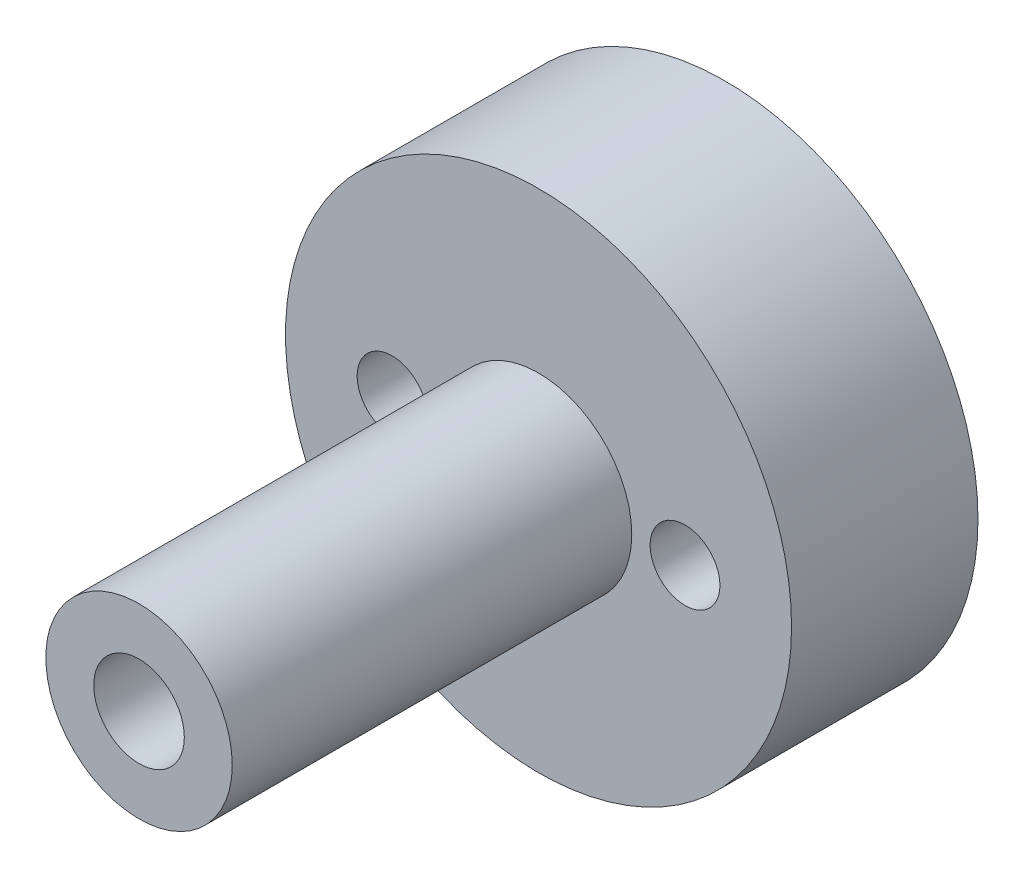
SolidWorks part; units mm, degrees
ref_plane "Front Plane" through (0, 0, 0) normal (0, 0, 1) x (1, 0, 0)
ref_plane "Top Plane" through (0, 0, 0) normal (0, 1, 0) x (1, 0, 0)
ref_plane "Right Plane" through (0, 0, 0) normal (1, 0, 0) x (0, 0, -1)
sketch "Sketch1" plane through (0, 0, 0) normal (0, 0, 1) x (1, 0, 0)
  circle A0 centre (0, 0) radius 7.6
  circle A1 centre (0, 0) radius 9.5
  dimension "D1" = 15.2
  dimension "D2" = 19
extrude "Boss-Extrude1" add sketch "Sketch1" along normal blind 5
sketch "Sketch2" plane through (0, 0, 5) normal (0, 0, 1) x (1, 0, 0)
  circle A0 centre (0, 0) radius 9.5 construction
  circle A1 centre (0, 0) radius 9.5
  circle A2 centre (0, 0) radius 1.31
  dimension "D1" = 2.62
extrude "Boss-Extrude2" add sketch "Sketch2" along normal blind 2
sketch "Sketch3" plane through (0, 0, 7) normal (0, 0, 1) x (1, 0, 0)
  circle A0 centre (-5.5, 0) radius 1.31
  circle A1 centre (5.5, 0) radius 1.31
  circle A2 centre (0, 0) radius 1.31 construction
  circle A3 centre (0, 0) radius 1.7
  circle A4 centre (0, 0) radius 3.5
  dimension "D1" = 5.5
  dimension "D3" = 3.4
  dimension "D4" = 7
  dimension "D2" = 5.5
extrude "Boss-Extrude3" add sketch "Sketch3" along normal blind 15 contours A4 A3 region at (-3.401, 0, 7)
extrude "Cut-Extrude1" cut sketch "Sketch3<3>" against normal through all both and the other way through all contours A0 | A1 region at (-5.5, 0, 7)
sketch "Sketch3<3>" plane through (0, 0, 7) normal (0, 0, 1) x (1, 0, 0) same geometry as "Sketch3"
sketch "Sketch4" plane through (0, 0, 5) normal (0, 0, -1) x (-1, 0, 0)
  circle A0 centre (-5.5, 0) radius 1.31 construction
  circle A1 centre (5.5, 0) radius 1.31 construction
  circle A2 centre (0, 0) radius 1.31 construction
  circle A3 centre (-5.5, 0) radius 1.31
  circle A4 centre (5.5, 0) radius 1.31
  circle A5 centre (0, 0) radius 1.31
  circle A6 centre (5.5, 0) radius 1.81
  circle A7 centre (0, 0) radius 1.81
  circle A8 centre (-5.5, 0) radius 1.81
  dimension "D1" = 0.5
extrude "Boss-Extrude4" add sketch "Sketch4" along normal up to surface (5 mm away) up to face at (9.5, 0, 0)
sketch "Sketch5" plane through (0, 0, 5) normal (0, 0, -1) x (-1, 0, 0)
  circle A0 centre (5.5, 0) radius 1.31 construction
  circle A1 centre (-5.5, 0) radius 1.31 construction
  circle A2 centre (0, 0) radius 1.31 construction
  circle A3 centre (5.5, 0) radius 1.31
  circle A4 centre (-5.5, 0) radius 1.31
  circle A5 centre (0, 0) radius 1.31
extrude "Boss-Extrude5" add sketch "Sketch5" along normal blind 0.15 and the other way blind 0.15
